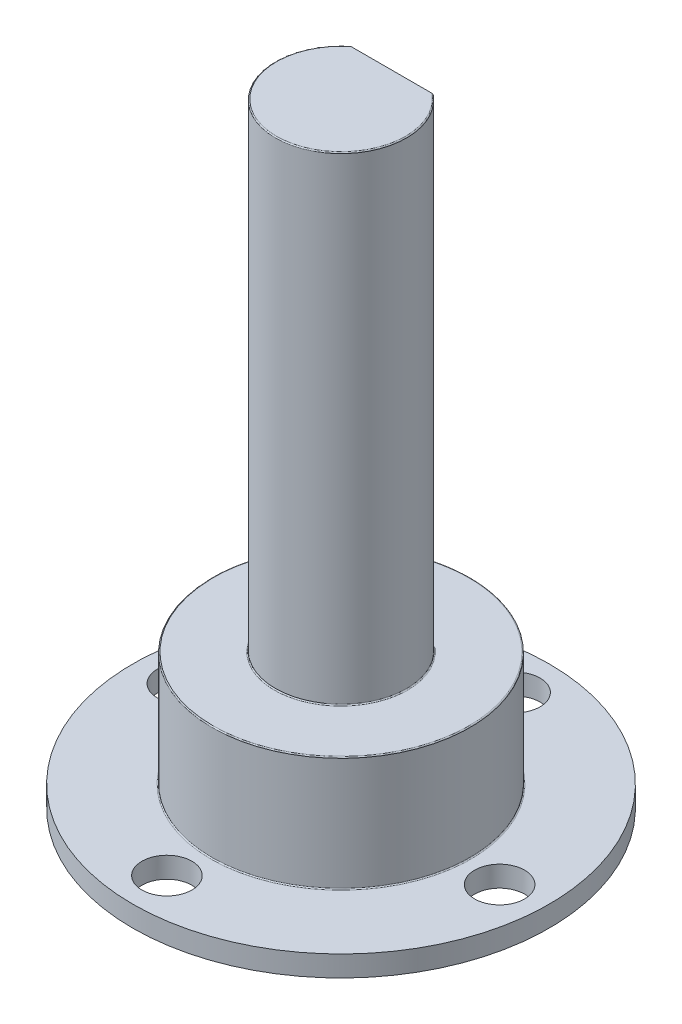
SolidWorks part; units mm, degrees
material "ABS"
ref_plane "Plan de face" through (0, 0, 0) normal (0, 0, 1) x (1, 0, 0)
ref_plane "Plan de dessus" through (0, 0, 0) normal (0, 1, 0) x (1, 0, 0)
ref_plane "Plan de droite" through (0, 0, 0) normal (1, 0, 0) x (0, 0, -1)
sketch "Esquisse2" plane through (0, 0, 0) normal (0, 0, 1) x (1, 0, 0)
  line L0 (0, 29.5) -> (3.15, 29.5)
  line L3 (6.2, 3) -> (6.2, 1)
  line L4 (6.2, 1) -> (10, 1)
  line L5 (10, 1) -> (10, 0)
  line L6 (10, 0) -> (4.5, 0)
  line L7 (4.5, 0) -> (4.5, 3)
  line L8 (4.5, 3) -> (0, 3)
  line L9 (0, 3) -> (0, 29.5)
  line L11 (3.15, 29.5) -> (3.15, 6.5)
  line L12 (3.15, 6.5) -> (6.2, 6.5)
  line L13 (6.2, 3) -> (6.2, 6.5)
  point P2 (1.575, 29.5)
  dimension "D1" = 10
  dimension "D2" = 29.5
  dimension "D3" = 0
  dimension "D4" = 1
  dimension "D5" = 4.5
  dimension "D6" = 2
  dimension "D7" = 6.5
  dimension "D8" = 3
  dimension "D9" = 3.15
  dimension "D10" = 0
  dimension "D12" = 1.7
revolve "Révolution2" add sketch "Esquisse2" angle 360 about L9
sketch "Esquisse3" plane through (0, 29.5, 0) normal (0, 1, 0) x (1, 0, 0)
  line L1 (-3.6413, 2.4219) -> (2.9365, 2.4219)
  line L2 (-3.6413, 2.4219) -> (-3.6413, 3.808)
  line L3 (-3.6413, 3.808) -> (2.9365, 3.808)
  line L4 (2.9365, 2.4219) -> (2.9365, 3.808)
  dimension "D1" = 6.5779
extrude "Enlèv. mat.-Extru.1" cut sketch "Esquisse3" against normal up to surface (23 mm away) contours L4 L3 L2 L1 up to face at (0, 6.5, -3.15)
hole_wizard "Dégagement M21" positions "Esquisse4" profile "Esquisse5" hole size "M2" standard "Ansi Metric" end condition up to next
sketch "Esquisse4" plane through (0, 1, 0) normal (0, 1, 0) x (1, 0, 0)
  circle A0 centre (0, 0) radius 8 construction
  point P0 (0.3713, 7.9914)
  dimension "D1" = 16
sketch "Esquisse5" plane through (0.3713, 1, -7.9914) normal (1, 0, 0) x (0, 0, 1)
  line L0 (0, 0) -> (0, 1.001)
  line L1 (0, 1.001) -> (1.2, 1.001)
  line L2 (1.2, 1.001) -> (1.2, 0)
  line L5 (1.2, 0) -> (0, 0)
  line L11 (0, -6.35) -> (0, 107.95) construction
  dimension "Diamètre du perçage jusqu'au prochain" = 2.4
  dimension "Profondeur du perçage jusqu'au prochain" = 1.001
pattern_circular "Répétition circulaire1" count 4 over 360 about axis through (0, 1, 0) along (0, -1, 0) of "Dégagement M21"
fillet "Congé1" radius 0.05 4 edges at (0, 6.5, 3.15) (0, 6.5, -6.2) (0, 1, -6.2) (0, 29.5, 3.15)
